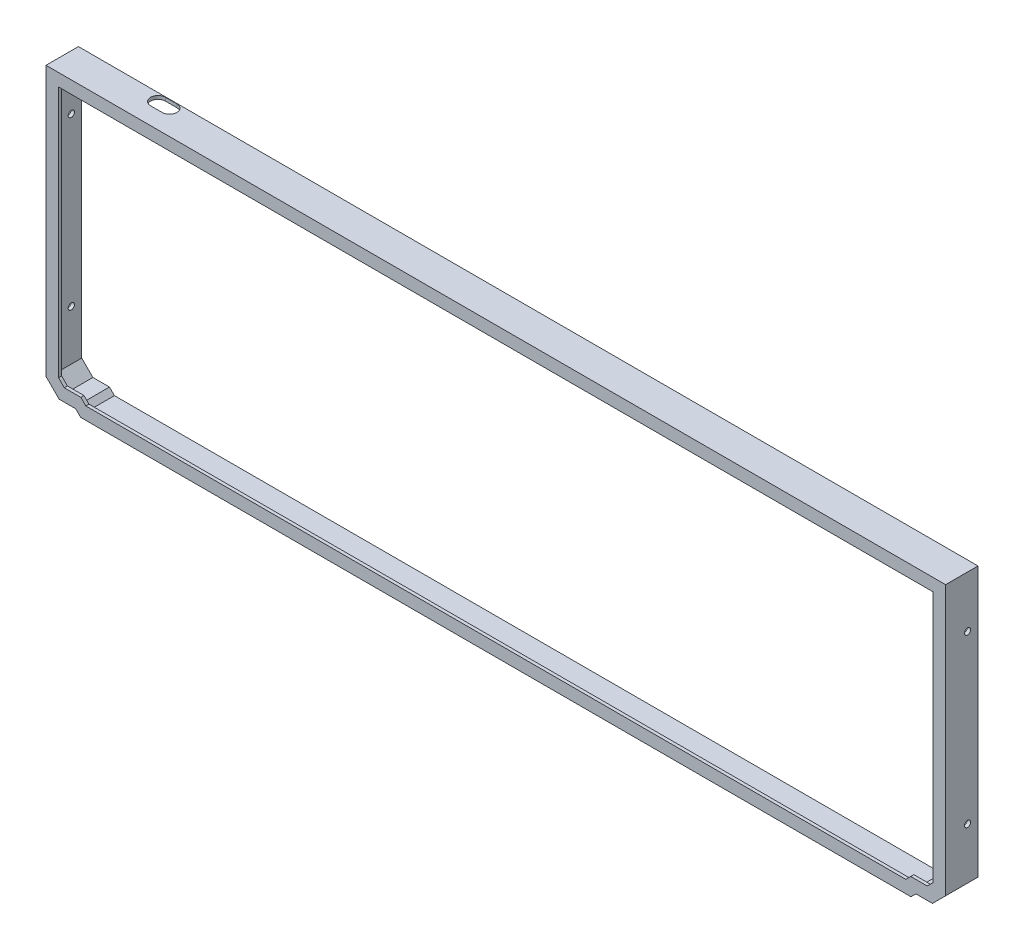
SolidWorks part; units mm, degrees
ref_plane "Přední rovina" through (0, 0, 0) normal (0, 0, 1) x (1, 0, 0)
ref_plane "Horní rovina" through (0, 0, 0) normal (0, 1, 0) x (1, 0, 0)
ref_plane "Pravá rovina" through (0, 0, 0) normal (1, 0, 0) x (0, 0, -1)
sketch "Skica1" plane through (0, 0, 0) normal (0, 0, 1) x (1, 0, 0)
  line L0 (0, 0) -> (428.28, 0) construction
  line L1 (0, 0) -> (0, -126.92) construction
  line L2 (428.28, 0) -> (428.28, -126.92) construction
  line L3 (0, -126.92) -> (5.3104, -132.2304) construction
  line L4 (428.28, -126.92) -> (422.9696, -132.2304) construction
  line L5 (5.3104, -132.2304) -> (13.2504, -132.2304) construction
  line L6 (422.9696, -132.2304) -> (415.0296, -132.2304) construction
  line L7 (13.2504, -132.2304) -> (15.6333, -134.6133) construction
  line L8 (415.0296, -132.2304) -> (412.6467, -134.6133) construction
  line L9 (412.6467, -134.6133) -> (15.6333, -134.6133) construction
  line L10 (-0.1, 0.1) -> (428.38, 0.1)
  line L11 (428.38, 0.1) -> (428.38, -126.9614)
  line L12 (428.38, -126.9614) -> (423.011, -132.3304)
  line L13 (423.011, -132.3304) -> (415.071, -132.3304)
  line L14 (415.071, -132.3304) -> (412.6881, -134.7133)
  line L15 (412.6881, -134.7133) -> (15.5919, -134.7133)
  line L16 (13.209, -132.3304) -> (15.5919, -134.7133)
  line L17 (5.269, -132.3304) -> (13.209, -132.3304)
  line L18 (-0.1, -126.9614) -> (5.269, -132.3304)
  line L19 (-0.1, 0.1) -> (-0.1, -126.9614)
  line L20 (-1.7, 1.7) -> (429.98, 1.7)
  line L21 (429.98, 1.7) -> (429.98, -127.6242)
  line L22 (429.98, -127.6242) -> (423.6738, -133.9304)
  line L23 (423.6738, -133.9304) -> (415.7338, -133.9304)
  line L24 (415.7338, -133.9304) -> (413.3508, -136.3133)
  line L25 (413.3508, -136.3133) -> (14.9292, -136.3133)
  line L26 (12.5462, -133.9304) -> (14.9292, -136.3133)
  line L27 (4.6062, -133.9304) -> (12.5462, -133.9304)
  line L28 (-1.7, -127.6242) -> (4.6062, -133.9304)
  line L29 (-1.7, 1.7) -> (-1.7, -127.6242)
  dimension "D1" = 428.28
  dimension "D2" = 126.92
  dimension "D3" = 126.92
  dimension "D4" = 7.51
  dimension "D5" = 7.51
  dimension "D6" = 135
  dimension "D7" = 135
  dimension "D8" = 7.94
  dimension "D9" = 7.94
  dimension "D10" = 3.37
  dimension "D11" = 3.37
  dimension "D12" = 135
  dimension "D13" = 0.1
  dimension "D14" = 1.6
extrude "Přidat vysunutím1" add sketch "Skica1" against normal blind 14.05
sketch "Skica2" plane through (0, 0, 0) normal (0, 0, 1) x (1, 0, 0)
  line L20 (4.3, -4.3) -> (4.3, -125.1389)
  line L21 (4.3, -125.1389) -> (7.0915, -127.9304)
  line L22 (7.0915, -127.9304) -> (15.0315, -127.9304)
  line L23 (15.0315, -127.9304) -> (17.4144, -130.3133)
  line L24 (17.4144, -130.3133) -> (410.8656, -130.3133)
  line L25 (410.8656, -130.3133) -> (413.2485, -127.9304)
  line L26 (413.2485, -127.9304) -> (421.1885, -127.9304)
  line L27 (421.1885, -127.9304) -> (423.98, -125.1389)
  line L28 (423.98, -125.1389) -> (423.98, -4.3)
  line L29 (423.98, -4.3) -> (4.3, -4.3)
  line L30 (4.3, -4.3) -> (4.3, -125.1389)
  line L31 (4.3, -125.1389) -> (7.0915, -127.9304)
  line L32 (7.0915, -127.9304) -> (15.0315, -127.9304)
  line L33 (15.0315, -127.9304) -> (17.4144, -130.3133)
  line L34 (17.4144, -130.3133) -> (410.8656, -130.3133)
  line L35 (410.8656, -130.3133) -> (413.2485, -127.9304)
  line L36 (413.2485, -127.9304) -> (421.1885, -127.9304)
  line L37 (421.1885, -127.9304) -> (423.98, -125.1389)
  line L38 (423.98, -125.1389) -> (423.98, -4.3)
  line L39 (423.98, -4.3) -> (4.3, -4.3)
  line L50 (-1.7, 1.7) -> (-1.7, -127.6242)
  line L51 (-1.7, -127.6242) -> (4.6062, -133.9304)
  line L52 (4.6062, -133.9304) -> (12.5462, -133.9304)
  line L53 (12.5462, -133.9304) -> (14.9292, -136.3133)
  line L54 (14.9292, -136.3133) -> (413.3508, -136.3133)
  line L55 (413.3508, -136.3133) -> (415.7338, -133.9304)
  line L56 (415.7338, -133.9304) -> (423.6738, -133.9304)
  line L57 (423.6738, -133.9304) -> (429.98, -127.6242)
  line L58 (429.98, -127.6242) -> (429.98, 1.7)
  line L59 (429.98, 1.7) -> (-1.7, 1.7)
  line L60 (-1.7, 1.7) -> (-1.7, -127.6242)
  line L61 (-1.7, -127.6242) -> (4.6062, -133.9304)
  line L62 (4.6062, -133.9304) -> (12.5462, -133.9304)
  line L63 (12.5462, -133.9304) -> (14.9292, -136.3133)
  line L64 (14.9292, -136.3133) -> (413.3508, -136.3133)
  line L65 (413.3508, -136.3133) -> (415.7338, -133.9304)
  line L66 (415.7338, -133.9304) -> (423.6738, -133.9304)
  line L67 (423.6738, -133.9304) -> (429.98, -127.6242)
  line L68 (429.98, -127.6242) -> (429.98, 1.7)
  line L69 (429.98, 1.7) -> (-1.7, 1.7)
  dimension "D1" = 6
  dimension "D2" = 0
extrude "Přidat vysunutím2" add sketch "Skica2" along normal blind 1.5
sketch "Skica3" plane through (0, 1.7, 0) normal (0, 1, 0) x (1, 0, 0)
  line L0 (-1.7, 10.3) -> (43.01, 10.3) construction
  line L1 (-1.7, 14.05) -> (-1.7, -1.5) construction
  line L2 (429.98, -1.5) -> (-1.7, -1.5) construction
  line L3 (45.76, 10.3) -> (40.26, 10.3) construction
  line L4 (45.76, 6.75) -> (40.26, 6.75)
  line L5 (45.76, 13.85) -> (40.26, 13.85)
  arc A0 (45.76, 6.75) -> (45.76, 13.85) centre (45.76, 10.3) ccw
  arc A1 (40.26, 13.85) -> (40.26, 6.75) centre (40.26, 10.3) ccw
  point P6 (40.26, 10.3)
  point P9 (43.01, 10.3)
  point P14 (36.71, 10.3)
  point P15 (49.31, 10.3)
  dimension "D1" = 11.8
  dimension "D2" = 44.71
  dimension "D3" = 2.75
  dimension "D4" = 7.1
extrude "Odebrat vysunutím1" cut sketch "Skica3" against normal up to surface (1.6 mm away) up to face at (214.14, 0.1, -7.025)
sketch "Skica4" plane through (-1.7, 0, 0) normal (-1, 0, 0) x (0, 0, 1)
  line L0 (-14.05, -62.9621) -> (1.5, -62.9621) construction
  line L1 (-14.05, 1.7) -> (-14.05, -127.6242) construction
  line L2 (1.5, 1.7) -> (1.5, -127.6242) construction
  circle A0 centre (-9.05, -22.9621) radius 1.5
  circle A1 centre (-9.05, -102.9621) radius 1.5
  dimension "D2" = 3
  dimension "D3" = 3
  dimension "D1" = 40
  dimension "D4" = 5
extrude "Odebrat vysunutím2" cut sketch "Skica4" against normal up to surface (431.68 mm away) up to face at (429.98, -62.9621, -6.275)
